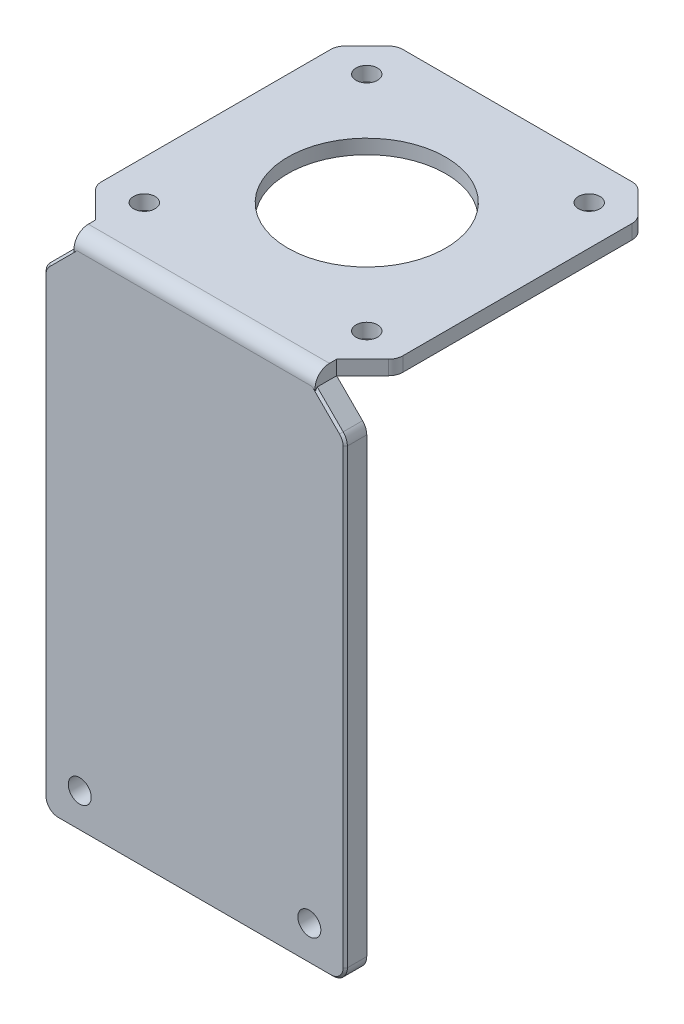
SolidWorks part; units mm, degrees
ref_plane "前视基准面" through (0, 0, 0) normal (0, 0, 1) x (1, 0, 0)
ref_plane "上视基准面" through (0, 0, 0) normal (0, 1, 0) x (1, 0, 0)
ref_plane "右视基准面" through (0, 0, 0) normal (1, 0, 0) x (0, 0, -1)
other "Configuration Table"
sketch "草图1" plane through (0, 0, 0) normal (0, 1, 0) x (1, 0, 0)
  line L0 (16.8, 21) -> (-16.8, 21)
  line L2 (-21, 16.8) -> (-21, -16.8)
  line L4 (-16.8, -21) -> (16.8, -21)
  line L6 (21, -16.8) -> (21, 16.8)
  line L8 (-1713.4156, 0) -> (83957.3648, 0) construction
  line L9 (0, -1728.3973) -> (0, 83942.3831) construction
  line L10 (-21, 16.8) -> (-16.8, 21)
  line L11 (16.8, 21) -> (21, 16.8)
  line L12 (16.8, -21) -> (21, -16.8)
  line L13 (-21, -16.8) -> (-16.8, -21)
  circle A2 centre (0, 0) radius 11
  circle A3 centre (-15.5, 15.5) radius 1.5
  circle A4 centre (15.5, 15.5) radius 1.5
  circle A5 centre (15.5, -15.5) radius 1.5
  circle A6 centre (-15.5, -15.5) radius 1.5
  point P10 (0, 0)
  point P18 (0, 0)
  point P19 (0, 0)
  point P20 (0, 0)
  point P21 (0, 0)
  point P23 (0, 0)
  point P24 (0, 0)
  point P25 (0, 0)
  point P26 (0, 0)
  point P27 (0, 0)
  point P28 (0, 0)
  point P30 (31.165, -23.2668)
  point P31 (-13.2287, -25.1469)
  dimension "D1" = 3
  dimension "D2" = 5.5
  dimension "D3" = 5.5
  dimension "D6" = 22
  dimension "D4" = 42
  dimension "D5" = 42
  dimension "D7" = 21
  dimension "D8" = 21
  dimension "D9" = 4.2
  dimension "D10" = 4.2
  dimension "D11" = 4.2
  dimension "D12" = 4.2
  dimension "D13" = 4.2
  dimension "D14" = 4.2
  dimension "D15" = 4.2
  dimension "D16" = 4.2
extrude "凸台-拉伸1" add sketch "草图1" along normal blind 2
sketch "草图2" plane through (0, 0, 21) normal (0, 0, 1) x (1, 0, 0)
  line L0 (-21, 2) -> (-21, 0) construction
  line L1 (-21, -70) -> (21, -70)
  line L2 (-21, -70) -> (-21, -4.2)
  line L3 (-16.8, 2) -> (16.8, 2)
  line L4 (21, -70) -> (21, -4.2)
  line L5 (21, 2) -> (21, 0) construction
  line L7 (-16.8, 2) -> (16.8, 2) construction
  line L8 (-16.8, 0) -> (16.8, 0) construction
  line L9 (-16.8, 0) -> (-21, -4.2)
  line L10 (-16.8, 0) -> (-16.8, 2)
  line L11 (0, -1000) -> (0, 49000) construction
  line L12 (16.8, 0) -> (21, -4.2)
  line L13 (16.8, 0) -> (16.8, 2)
  dimension "D1" = 70
extrude "凸台-拉伸2" add sketch "草图2" along normal blind 3
fillet "圆角1" radius 2 1 edges at (0, 2, 24)
fillet "圆角2" radius 2 2 edges at (-21, -70, 22.5) (21, -70, 22.5)
fillet "圆角3" radius 2 8 edges at (21, -4.2, 22.5) (21, 1, 16.8) (-21, -4.2, 22.5) (-21, 1, 16.8) (21, 1, -16.8) (16.8, 1, -21) (-16.8, 1, -21) (-21, 1, -16.8)
chamfer "倒角1" distance 0.3 angle 45 9 edges at (-18.6071, -1.8071, 24) (-20.8478, -4.2631, 24) (-21, -36.5142, 24) (-20.4142, -69.4142, 24) (0, -70, 24) (20.4142, -69.4142, 24) (18.6071, -1.8071, 24) (20.8478, -4.2631, 24) (21, -36.5142, 24)
sketch "草图3" plane through (0, 0, 21) normal (0, 0, -1) x (-1, 0, 0)
  line L0 (19, -70) -> (-19, -70) construction
  line L1 (-21, -68) -> (-21, -5.0284) construction
  line L2 (21, -5.0284) -> (21, -68) construction
  circle A0 centre (-16, -65) radius 1.6
  circle A1 centre (16, -65) radius 1.6
  dimension "D1" = 3.2
  dimension "D2" = 3.2
  dimension "D3" = 5
  dimension "D4" = 5
  dimension "D5" = 5
  dimension "D6" = 5
extrude "切除-拉伸1" cut sketch "草图3" against normal blind 3
